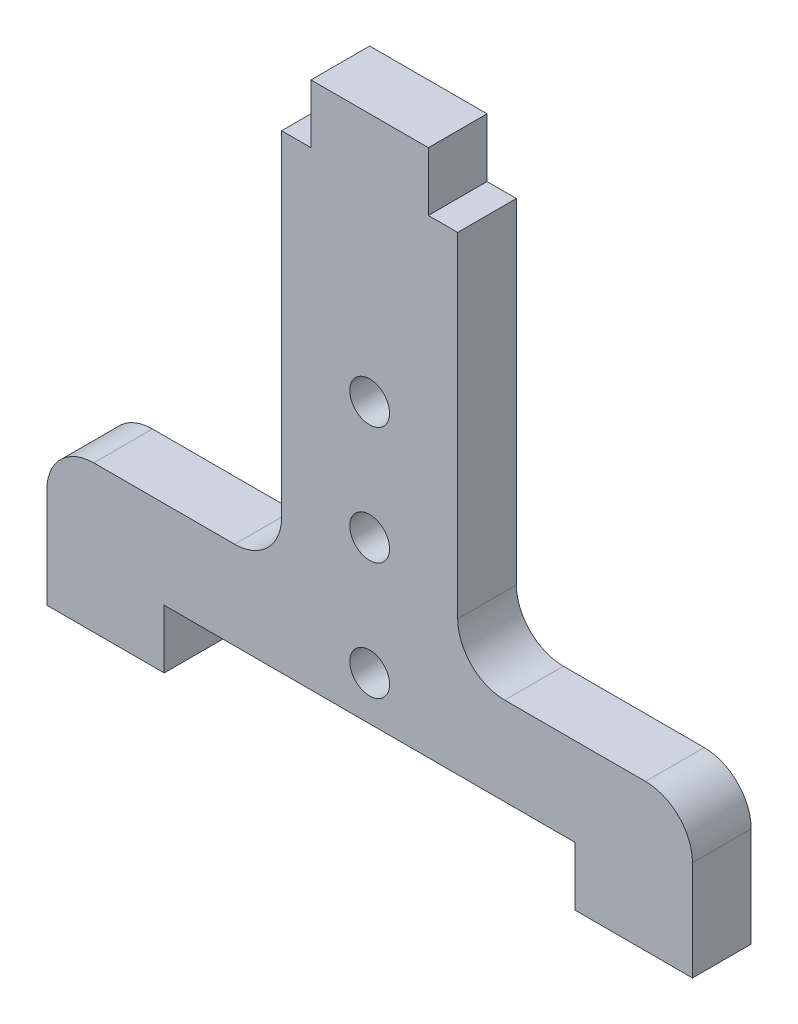
SolidWorks part; units mm, degrees
material "Custom Plastic"
ref_plane "Front Plane" through (0, 0, 0) normal (0, 0, 1) x (1, 0, 0)
ref_plane "Top Plane" through (0, 0, 0) normal (0, 1, 0) x (1, 0, 0)
ref_plane "Right Plane" through (0, 0, 0) normal (1, 0, 0) x (0, 0, -1)
sketch "Sketch1" plane through (0, 0, 0) normal (0, 0, 1) x (1, 0, 0)
  line L1 (-34.925, -25.4) -> (34.925, -25.4)
  line L2 (-34.925, -25.4) -> (-34.925, 25.4)
  line L3 (-34.925, 25.4) -> (34.925, 25.4)
  line L4 (34.925, -25.4) -> (34.925, 25.4)
  line L5 (-34.925, -25.4) -> (34.925, 25.4) construction
  line L6 (-34.925, 25.4) -> (34.925, -25.4) construction
  point P0 (0, 0)
  dimension "D1" = 69.85
  dimension "D2" = 50.8
extrude "Base" add sketch "Sketch1" along normal blind 6.35
sketch "Sketch6" plane through (0, 0, 6.35) normal (0, 0, 1) x (1, 0, 0)
  line L0 (34.925, 25.4) -> (-34.925, 25.4) construction
  line L1 (-6.35, 25.4) -> (6.35, 25.4)
  line L2 (-6.35, 25.4) -> (-6.35, 31.75)
  line L3 (-6.35, 31.75) -> (6.35, 31.75)
  line L4 (6.35, 25.4) -> (6.35, 31.75)
  line L5 (0, -25.4) -> (0, 25.4) construction
  line L6 (-34.925, -25.4) -> (34.925, -25.4) construction
  line L7 (22.225, -25.4) -> (22.225, -31.75)
  line L8 (-34.925, -25.4) -> (-22.225, -25.4)
  line L9 (-34.925, -25.4) -> (-34.925, -31.75)
  line L10 (-34.925, -31.75) -> (-22.225, -31.75)
  line L11 (-22.225, -25.4) -> (-22.225, -31.75)
  line L12 (34.925, -31.75) -> (22.225, -31.75)
  line L13 (34.925, -25.4) -> (34.925, -31.75)
  line L14 (34.925, -25.4) -> (22.225, -25.4)
  point P7 (0, 25.4)
  dimension "D1" = 12.7
  dimension "D2" = 6.35
  dimension "D3" = 6.35
  dimension "D4" = 12.7
extrude "Boss-Extrude1" add sketch "Sketch6" against normal blind 6.35
sketch "Sketch7" plane through (0, 0, 6.35) normal (0, 0, 1) x (1, 0, 0)
  line L1 (-6.35, 25.4) -> (-34.925, 25.4) construction
  line L2 (-9.525, 25.4) -> (-9.525, -15.875)
  line L4 (-9.525, -15.875) -> (-34.925, -15.875)
  line L5 (-34.925, 25.4) -> (-34.925, -31.75) construction
  line L6 (-22.225, -25.4) -> (22.225, -25.4) construction
  line L7 (0, -25.4) -> (0, 31.75) construction
  line L8 (6.35, 31.75) -> (-6.35, 31.75) construction
  line L9 (-9.525, 25.4) -> (-34.925, 25.4)
  line L10 (-34.925, 25.4) -> (-34.925, -15.875)
  dimension "D1" = 9.525
  dimension "D2" = 9.525
extrude "Cut-Extrude1" cut sketch "Sketch7" against normal through all
sketch "Motor mounting sketch" plane through (0, 0, 6.35) normal (0, 0, 1) x (1, 0, 0)
  line L0 (-34.925, -20.6375) -> (34.925, -20.6375) construction
  line L1 (34.925, -31.75) -> (34.925, 25.4) construction
  line L2 (-34.925, -15.875) -> (-34.925, -31.75) construction
  line L3 (0, 30.121) -> (0, -20.6375) construction
  line L7 (-22.225, -25.4) -> (22.225, -25.4) construction
  point P12 (0, -20.6375)
  point P15 (0, 17.4625)
  point P20 (0, -7.9375)
  point P21 (0, 4.7625)
  dimension "D1" = 4.7625
  dimension "D2" = 12.7
  dimension "D3" = 12.7
  dimension "D4" = 90
  dimension "D5" = 12.7
hole_wizard "#8 Clearance Hole1" positions "Sketch5" profile "Sketch4" hole size "#8" standard "ANSI Inch" end condition through all
sketch "Sketch5" plane through (0, 0, 0) normal (0, 0, -1) x (-1, 0, 0)
  point P3 (0, -20.6375)
  point P31 (0, -7.9375)
  point P34 (0, 4.7625)
sketch "Sketch4" plane through (0, -20.6375, 0) normal (1, 0, 0) x (0, 1, 0)
  line L0 (0, 0) -> (0, 6.35)
  line L1 (0, 6.35) -> (2.1526, 6.35)
  line L2 (2.1526, 6.35) -> (2.1526, 0)
  line L5 (2.1526, 0) -> (0, 0)
  line L11 (0, -6.35) -> (0, 107.95) construction
  dimension "Thru Hole Dia." = 4.3053
  dimension "Thru Hole Depth" = 6.35
sketch "Sketch8" plane through (0, 0, 6.35) normal (0, 0, 1) x (1, 0, 0)
  line L0 (9.525, 25.4) -> (9.525, -15.875)
  line L1 (34.925, 25.4) -> (6.35, 25.4) construction
  line L2 (6.35, 25.4) -> (6.35, 31.75) construction
  line L4 (9.525, -15.875) -> (34.925, -15.875)
  line L5 (34.925, -31.75) -> (34.925, 25.4) construction
  line L6 (34.925, -15.875) -> (34.925, 25.4)
  line L7 (34.925, 25.4) -> (9.525, 25.4)
  line L9 (-34.925, -15.875) -> (-9.525, -15.875) construction
  point P1 (6.35, 28.575)
  dimension "D1" = 3.175
extrude "Cut-Extrude2" cut sketch "Sketch8" against normal through all
fillet "Fillet1" radius 5.08 4 edges at (9.525, -15.875, 3.175) (34.925, -15.875, 3.175) (-34.925, -15.875, 3.175) (-9.525, -15.875, 3.175)
equation "\"MAT_THICKNESS\"=0.25"
equation "\"D1@Base\"=\"MAT_THICKNESS\""
equation "\"D2@Sketch6\" = \"MAT_THICKNESS\""
equation "\"D3@Sketch6\"=\"MAT_THICKNESS\""
equation "\"D1@Boss-Extrude1\"=\"MAT_THICKNESS\""
